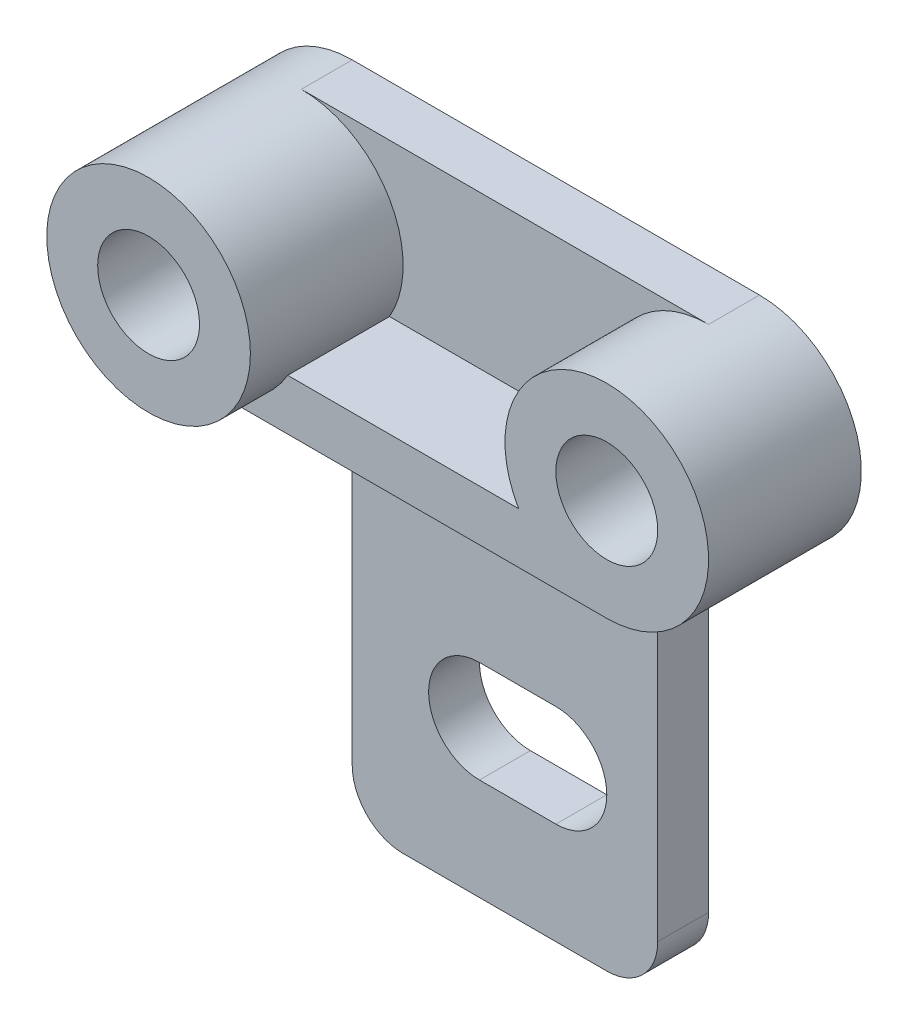
SolidWorks part; units mm, degrees
ref_plane "Front Plane" through (0, 0, 0) normal (0, 0, 1) x (1, 0, 0)
ref_plane "Top Plane" through (0, 0, 0) normal (0, 1, 0) x (1, 0, 0)
ref_plane "Right Plane" through (0, 0, 0) normal (1, 0, 0) x (0, 0, -1)
sketch "Sketch1" plane through (0, 0, 0) normal (0, 0, 1) x (1, 0, 0)
  circle A0 centre (-40, 3.0005) radius 20
  circle A1 centre (40, 3.0005) radius 20
  point P4 (0, 0)
  point P6 (0, 0)
  point P7 (0, 0)
  point P8 (0, 0)
  point P9 (0, 0)
  dimension "D2" = 40
  dimension "D3" = 40
  dimension "D1" = 40
  dimension "D4" = 80
extrude "Boss-Extrude1" add sketch "Sketch1" along normal blind 30 contours A1
extrude "Boss-Extrude2" add sketch "Sketch1<4>" along normal blind 40 separate body contours A0
sketch "Sketch1<4>" plane through (0, 0, 0) normal (0, 0, 1) x (1, 0, 0) same geometry as "Sketch1"
sketch "Sketch2" plane through (0, 0, 0) normal (0, 0, -1) x (-1, 0, 0)
  line L1 (-40, 23.0005) -> (40, 23.0005)
  line L2 (-40, 23.0005) -> (-40, -16.9995)
  line L3 (-40, -16.9995) -> (40, -16.9995)
  line L4 (40, 23.0005) -> (40, -16.9995)
  circle A0 centre (-40, 3.0005) radius 20 construction
  circle A1 centre (40, 3.0005) radius 20 construction
extrude "Boss-Extrude3" add sketch "Sketch2" against normal blind 10
sketch "Sketch3" plane through (0, 0, 10) normal (0, 0, 1) x (1, 0, 0)
  line L1 (40, -16.9995) -> (-40, -16.9995)
  line L2 (40, -16.9995) -> (40, -6.9995)
  line L3 (40, -6.9995) -> (-40, -6.9995)
  line L4 (-40, -16.9995) -> (-40, -6.9995)
  dimension "D1" = 10
extrude "Boss-Extrude4" add sketch "Sketch3" along normal blind 20
sketch "Sketch4" plane through (0, -16.9995, 0) normal (0, -1, 0) x (1, 0, 0)
  line L0 (60, 0) -> (20, 0) construction
  line L1 (-30, 10) -> (30, 10)
  line L2 (-30, 10) -> (-30, 0)
  line L3 (-30, 0) -> (30, 0)
  line L4 (30, 10) -> (30, 0)
  line L5 (-40, 30) -> (-40, 0) construction
  dimension "D1" = 10
  dimension "D2" = 60
  dimension "D3" = 10
sketch "Sketch6" plane through (0, 0, 10) normal (0, 0, 1) x (1, 0, 0)
  line L0 (-30, -16.9995) -> (30, -16.9995) construction
  line L1 (-30, -16.9995) -> (30, -16.9995)
  line L2 (-30, -16.9995) -> (-30, -86.9995)
  line L3 (-20, -96.9995) -> (20, -96.9995)
  line L4 (30, -16.9995) -> (30, -86.9995)
  line L5 (-30, -16.9995) -> (30, -16.9995) construction
  arc A0 (20, -96.9995) -> (30, -86.9995) centre (20, -86.9995) ccw
  arc A1 (-30, -86.9995) -> (-20, -96.9995) centre (-20, -86.9995) ccw
  point P12 (-30, -96.9995)
  dimension "D2" = 10
  dimension "D1" = 80
extrude "Boss-Extrude7" add sketch "Sketch6" against normal blind 10
sketch "Sketch7" plane through (0, 0, 10) normal (0, 0, 1) x (1, 0, 0)
  line L0 (-5, -66.9995) -> (10, -66.9995) construction
  line L1 (-5, -56.9995) -> (10, -56.9995)
  line L2 (-5, -76.9995) -> (10, -76.9995)
  line L3 (30, -86.9995) -> (30, -16.9995) construction
  line L4 (-20, -96.9995) -> (20, -96.9995) construction
  arc A0 (-5, -56.9995) -> (-5, -76.9995) centre (-5, -66.9995) ccw
  arc A1 (10, -76.9995) -> (10, -56.9995) centre (10, -66.9995) ccw
  point P2 (2.5, -66.9995)
  point P7 (0, 0)
  point P9 (57.7551, -70.5485)
  dimension "D4" = 10
  dimension "D1" = 15
  dimension "D2" = 20
  dimension "D3" = 30
extrude "Cut-Extrude3" cut sketch "Sketch7" against normal blind 10
hole_wizard "#97 (0.78740157) Diameter Hole1" positions "Sketch11" profile "Sketch13" hole size "#97" standard "ANSI Inch" end condition through all
sketch "Sketch11" plane through (0, 0, 0) normal (0, 0, -1) x (-1, 0, 0)
  point P0 (-40, 3.0005)
  point P3 (40, 3.0005)
sketch "Sketch13" plane through (40, 3.0005, 0) normal (1, 0, 0) x (0, 1, 0)
  line L0 (0, 0) -> (0, 40)
  line L1 (0, 40) -> (10, 40)
  line L2 (10, 40) -> (10, 0)
  line L5 (10, 0) -> (0, 0)
  line L11 (0, -6.35) -> (0, 107.95) construction
  dimension "Thru Hole Dia." = 20
  dimension "Thru Hole Depth" = 40
